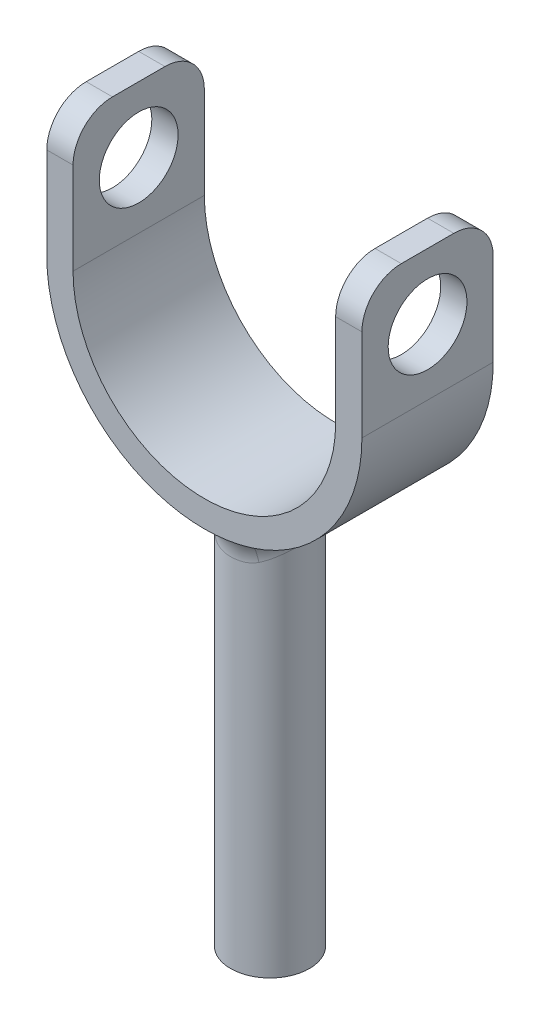
SolidWorks part; units mm, degrees
material "AISI 1020"
ref_plane "Alzado" through (0, 0, 0) normal (0, 0, 1) x (1, 0, 0)
ref_plane "Planta" through (0, 0, 0) normal (0, 1, 0) x (1, 0, 0)
ref_plane "Vista lateral" through (0, 0, 0) normal (1, 0, 0) x (0, 0, -1)
sketch "Croquis1" plane through (0, 0, 0) normal (0, 0, 1) x (1, 0, 0)
  line L0 (-50, 0) -> (-50, 50)
  line L1 (-50, 50) -> (-60, 50)
  line L2 (-60, 50) -> (-60, 0)
  line L5 (-50, 0) -> (50, 0) construction
  line L6 (50, 0) -> (50, 50)
  line L7 (50, 50) -> (60, 50)
  line L8 (60, 50) -> (60, 0)
  arc A0 (-50, 0) -> (50, 0) centre (0, 0) ccw
  arc A1 (-60, 0) -> (60, 0) centre (0, 0) ccw
  dimension "D1" = 50
  dimension "D2" = 60
  dimension "D3" = 50
  dimension "D4" = 50
extrude "Saliente-Extruir1" add sketch "Croquis1" against normal blind 50
fillet "Redondeo1" radius 15 4 edges at (55, 50, -50) (55, 50, 0) (-55, 50, -50) (-55, 50, 0)
sketch "Croquis2" plane through (-60, 0, 0) normal (-1, 0, 0) x (0, 0, 1)
  line L2 (-35, 50) -> (-15, 50) construction
  line L3 (-50, 0) -> (0, 0) construction
  circle A0 centre (-25, 25) radius 15
  point P6 (-25, 0)
  dimension "D1" = 30
  dimension "D2" = 25
extrude "Cortar-Extruir1" cut sketch "Croquis2" against normal through all
sketch "Croquis3" plane through (0, 0, 0) normal (0, 0, 1) x (1, 0, 0)
  line L0 (0, 0) -> (0, -210) construction
  dimension "D1" = 210
ref_plane "Plano1" through (0, -210, 0) normal (0, 1, 0) x (1, 0, 0)
sketch "Croquis4" plane through (0, -210, 0) normal (0, 1, 0) x (1, 0, 0)
  line L0 (0, 0) -> (0, 50) construction
  line L1 (60, 50) -> (-60, 50) construction
  circle A0 centre (0, 25) radius 15
  dimension "D1" = 30
extrude "Saliente-Extruir2" add sketch "Croquis4" along normal up to next
fillet "Redondeo2" radius 15 1 edges at (-2.9337, -59.9282, -10.2897)
